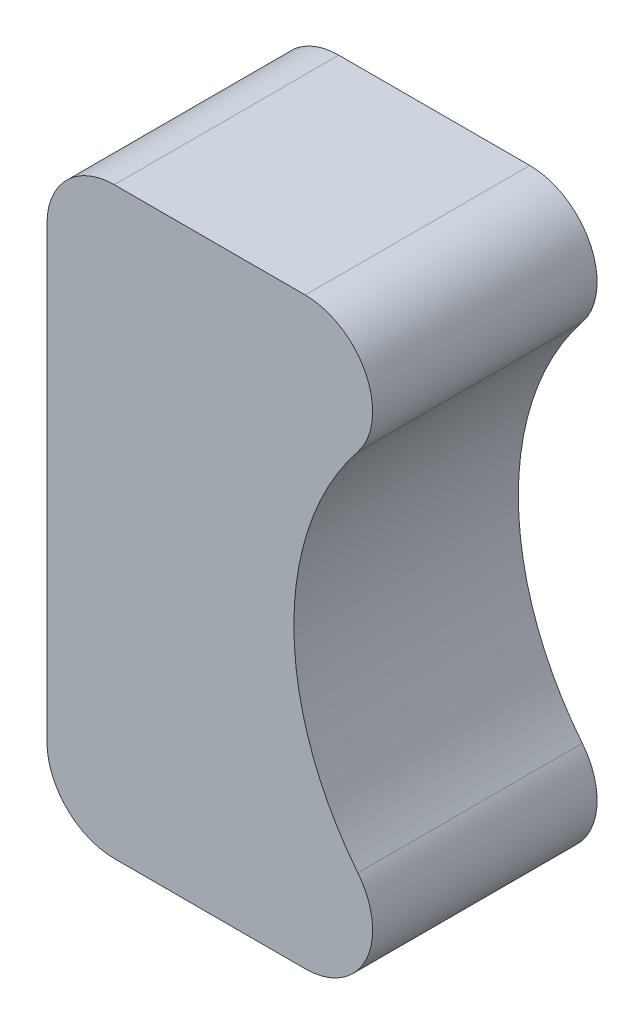
SolidWorks part; units mm, degrees
ref_plane "Front Plane" through (0, 0, 0) normal (0, 0, 1) x (1, 0, 0)
ref_plane "Top Plane" through (0, 0, 0) normal (0, 1, 0) x (1, 0, 0)
ref_plane "Right Plane" through (0, 0, 0) normal (1, 0, 0) x (0, 0, -1)
sketch "Sketch1" plane through (0, 0, 0) normal (0, 0, 1) x (1, 0, 0)
  line L1 (0, 0) -> (12, 0)
  line L2 (0, 0) -> (0, 13)
  line L3 (0, 13) -> (12, 13)
  line L4 (12, 0) -> (12, 13)
  dimension "D1" = 13
  dimension "D2" = 12
extrude "Boss-Extrude1" add sketch "Sketch1" along normal blind 5
sketch "Sketch3" plane through (0, 0, 5) normal (0, 0, 1) x (1, 0, 0)
  line L0 (0, 6.5) -> (12, 6.5) construction
  line L1 (0, 13) -> (0, 0) construction
  circle A0 centre (12, 6.5) radius 6.5
  dimension "D1" = 13
extrude "Cut-Extrude1" cut sketch "Sketch3" against normal blind 9
sketch "Sketch4" plane through (0, 0, 0) normal (-1, 0, 0) x (0, 0, 1)
  line L0 (2.5, 13) -> (2.5, 0) construction
  line L1 (5, 13) -> (0, 13) construction
  line L2 (5, 0) -> (0, 0) construction
  circle A0 centre (2.5, 6.5) radius 1.75
  dimension "D1" = 3.5
extrude "Cut-Extrude2" cut sketch "Sketch4" against normal blind 3
fillet "Fillet1" radius 1.5 2 edges at (12, 0, 2.5) (12, 13, 2.5)
fillet "Fillet2" radius 1.5 2 edges at (0, 0, 2.5) (0, 13, 2.5)
